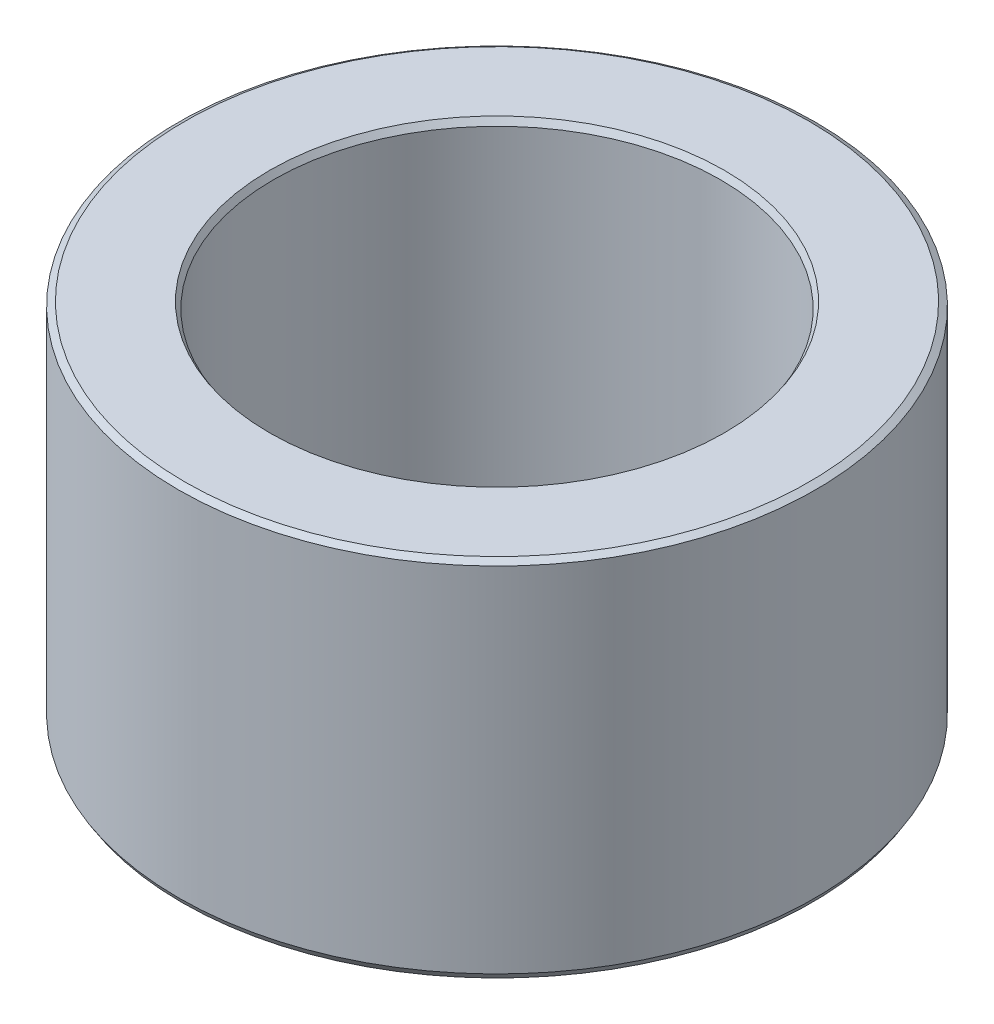
SolidWorks part; units mm, degrees
ref_plane "Front Plane" through (0, 0, 0) normal (0, 0, 1) x (1, 0, 0)
ref_plane "Top Plane" through (0, 0, 0) normal (0, 1, 0) x (1, 0, 0)
ref_plane "Right Plane" through (0, 0, 0) normal (1, 0, 0) x (0, 0, -1)
sketch "Sketch1" plane through (0, 0, 0) normal (0, 1, 0) x (1, 0, 0)
  circle A0 centre (0, 0) radius 52.5
  dimension "SLEEVE_OD" = 105
extrude "Boss-Extrude1" add sketch "Sketch1" along normal blind 59.8848
sketch "Sketch2" plane through (0, 0, 0) normal (0, 1, 0) x (1, 0, 0)
  circle A0 centre (0, 0) radius 36.8524
  dimension "BORE_D" = 73.7048
extrude "Cut-Extrude1" cut sketch "Sketch2" along normal through all
chamfer "Chamfer1" distance 0.6308 angle 58.4 4 edges at (0, 59.8848, 36.8524) (0, 0, 36.8524) (0, 0, 52.5) (0, 59.8848, 52.5) first distance on face at (0, 59.8848, 36.8524) first distance on face at (0, 0, 36.8524) first distance on face at (0, 59.8848, 52.5)
